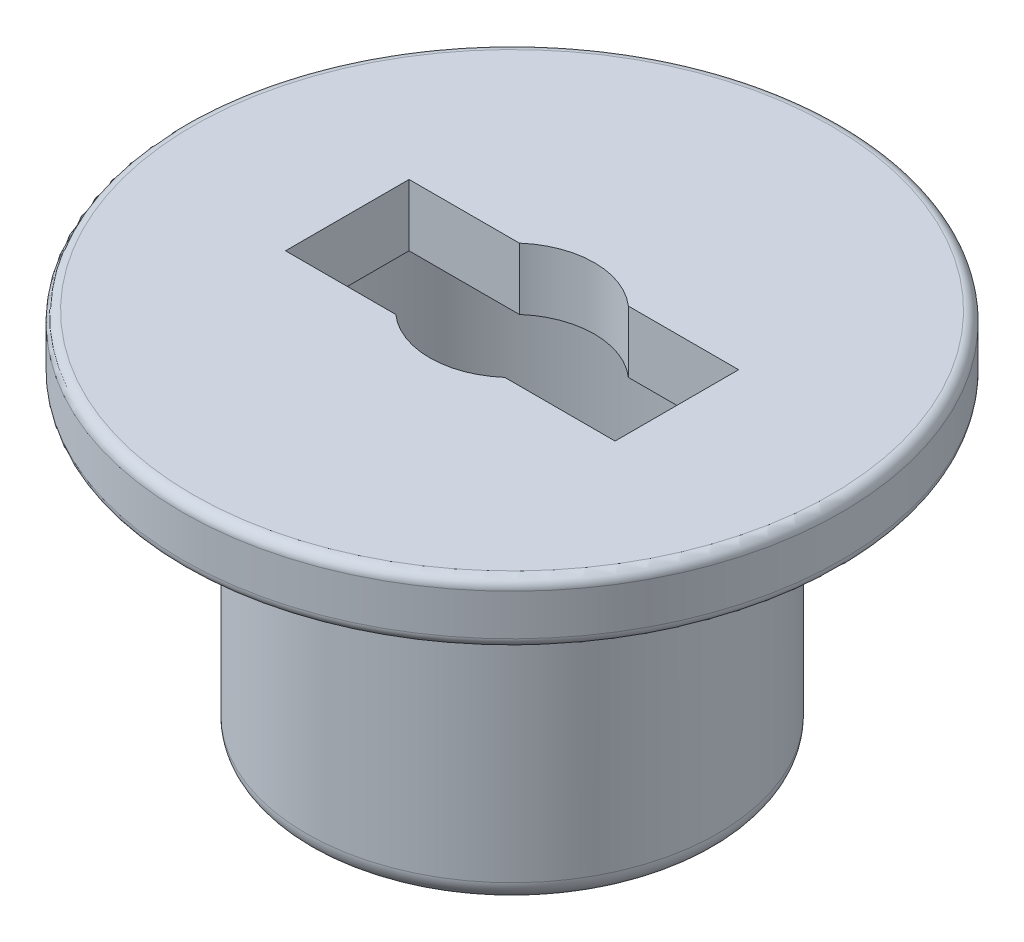
SolidWorks part; units mm, degrees
ref_plane "前视基准面" through (0, 0, 0) normal (0, 0, 1) x (1, 0, 0)
ref_plane "上视基准面" through (0, 0, 0) normal (0, 1, 0) x (1, 0, 0)
ref_plane "右视基准面" through (0, 0, 0) normal (1, 0, 0) x (0, 0, -1)
sketch "Sketch1" plane through (0, 0, 0) normal (0, 1, 0) x (1, 0, 0)
  line L0 (2.6458, 3) -> (8, 3)
  line L1 (-8, 3) -> (-2.6458, 3)
  line L2 (-8, 3) -> (-8, -3)
  line L3 (-8, -3) -> (-2.6458, -3)
  line L4 (8, 3) -> (8, -3)
  line L5 (2.6458, -3) -> (8, -3)
  line L6 (0, 0) -> (-16, 0) construction
  circle A0 centre (0, 0) radius 16
  arc A2 (-2.6458, -3) -> (2.6458, -3) centre (0, 0) ccw
  arc A3 (2.6458, 3) -> (-2.6458, 3) centre (0, 0) ccw
  dimension "D1" = 32
  dimension "D2" = 6
  dimension "D3" = 16
extrude "Boss-Extrude1" add sketch "Sketch1" along normal blind 3
sketch "Sketch3" plane through (0, 0, 0) normal (0, -1, 0) x (1, 0, 0)
  line L0 (0, 0) -> (-16, 0) construction
  circle A0 centre (0, 0) radius 16 construction
  circle A1 centre (-13, 0) radius 1
  dimension "D1" = 13
extrude "Boss-Extrude2" add sketch "Sketch3" along normal blind 3
sketch "Sketch4" plane through (0, 0, 0) normal (0, -1, 0) x (1, 0, 0)
  circle A0 centre (0, 0) radius 10
extrude "Boss-Extrude3" add sketch "Sketch4" along normal blind 15
sketch "Sketch5" plane through (0, 0, 0) normal (0, 1, 0) x (1, 0, 0)
  circle A0 centre (0, 0) radius 9
extrude "Cut-Extrude1" cut sketch "Sketch5" against normal up to next
fillet "Fillet1" radius 1 1 edges at (0, -15, -10)
fillet "Fillet2" radius 0.5 2 edges at (0, 0, 16) (0, 3, 16)
